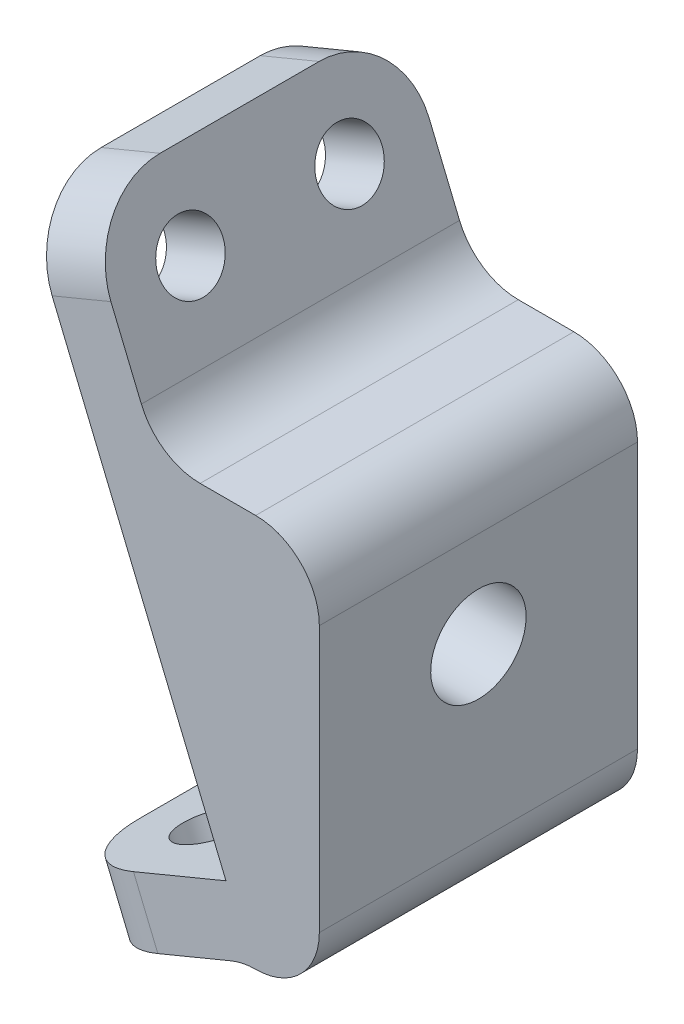
SolidWorks part; units mm, degrees
ref_plane "Front Plane" through (0, 0, 0) normal (0, 0, 1) x (1, 0, 0)
ref_plane "Top Plane" through (0, 0, 0) normal (0, 1, 0) x (1, 0, 0)
ref_plane "Right Plane" through (0, 0, 0) normal (1, 0, 0) x (0, 0, -1)
sketch "Sketch1" plane through (0, 0, 0) normal (0, 0, 1) x (1, 0, 0)
  line L0 (-41.4834, 17.183) -> (17.183, 41.4834) construction
  line L1 (-41.4834, 17.183) -> (-17.183, -41.4834) construction
  line L2 (17.183, 41.4834) -> (41.4834, -17.183) construction
  line L3 (-17.183, -41.4834) -> (41.4834, -17.183) construction
  line L4 (-41.4834, 17.183) -> (41.4834, -17.183) construction
  line L5 (17.183, 41.4834) -> (-17.183, -41.4834) construction
  line L6 (-17.183, -41.4834) -> (50.8, -41.4834) construction
  line L7 (50.8, -41.4834) -> (50.8, 41.4834) construction
  line L8 (50.8, 41.4834) -> (17.183, 41.4834) construction
  line L9 (17.183, 41.4834) -> (41.4834, -17.183) construction
  line L10 (41.4834, -17.183) -> (-17.183, -41.4834) construction
  line L11 (17.183, 41.4834) -> (-50.8, 41.4834) construction
  line L12 (-50.8, 41.4834) -> (-50.8, -41.4834) construction
  line L13 (-50.8, -41.4834) -> (-17.183, -41.4834) construction
  line L14 (0, 0) -> (50.8, 0) construction
  line L15 (50.8, 9.525) -> (50.8, -17.0005)
  line L17 (21.0981, 32.0315) -> (41.4834, -17.183)
  line L18 (41.4834, -17.183) -> (24.9233, -24.0424)
  line L19 (21.0981, 32.0315) -> (26.9647, 34.4615)
  line L20 (26.9647, 34.4615) -> (33.0398, 19.795)
  line L22 (24.9233, -24.0424) -> (27.3534, -29.909)
  line L23 (27.3534, -29.909) -> (42.02, -23.8339)
  line L25 (44.45, 15.875) -> (38.9064, 15.875)
  line L26 (44.45, -23.3505) -> (38.1323, -23.3505) construction
  line L27 (44.45, 9.525) -> (44.45, -17.0005) construction
  line L28 (50.8, 9.525) -> (60.325, 9.525) construction
  line L29 (60.325, 9.525) -> (60.325, 0) construction
  line L30 (60.325, 0) -> (50.8, 0) construction
  arc A0 (50.8, 9.525) -> (44.45, 15.875) centre (44.45, 9.525) ccw
  arc A1 (50.8, -17.0005) -> (44.45, -23.3505) centre (44.45, -17.0005) cw
  arc A2 (38.9064, 15.875) -> (33.0398, 19.795) centre (38.9064, 22.225) cw
  arc A3 (44.45, -23.3505) -> (42.02, -23.8339) centre (44.45, -29.7005) ccw
  point P1 (0, 0)
  point P25 (64.3855, 11.5127)
  point P31 (28.1797, 31.5282)
  dimension "D4" = 6.35
  dimension "D1" = 22.5
  dimension "D2" = 101.6
  dimension "D3" = 63.5
  dimension "D5" = 6.35
  dimension "D6" = 15.875
  dimension "D7" = 9.525
extrude "Boss-Extrude1" add sketch "Sketch1" along normal mid plane 31.75
sketch "Sketch3" plane through (35.1998, 14.5802, 0) normal (0.9239, 0.3827, 0) x (0, 0, -1)
  line L0 (-15.875, 21.5194) -> (15.875, 21.5194) construction
  line L1 (-15.875, 5.6444) -> (-15.875, 21.5194) construction
  line L2 (15.875, 5.6444) -> (15.875, 21.5194) construction
  line L3 (-15.875, 13.5819) -> (-15.875, 21.5194)
  line L4 (-15.875, 21.5194) -> (-7.9375, 21.5194)
  line L5 (7.9375, 21.5194) -> (15.875, 21.5194)
  line L6 (15.875, 21.5194) -> (15.875, 13.5819)
  arc A0 (-7.9375, 21.5194) -> (-15.875, 13.5819) centre (-7.9375, 13.5819) ccw
  arc A1 (7.9375, 21.5194) -> (15.875, 13.5819) centre (7.9375, 13.5819) cw
  circle A2 centre (-7.9375, 13.5819) radius 3.2385
  circle A3 centre (7.9375, 13.5819) radius 3.2385
  point P8 (-15.875, 13.5819)
  dimension "D1" = 6.477
extrude "Cut-Extrude1" cut sketch "Sketch3" against normal through all both and the other way through all
sketch "Sketch4" plane through (14.5802, -35.1998, 0) normal (0.3827, -0.9239, 0) x (-0.9239, -0.3827, 0)
  line L0 (-13.8255, -15.875) -> (-29.7005, -15.875) construction
  line L1 (-13.8255, 15.875) -> (-29.7005, 15.875) construction
  line L2 (-13.8255, -15.875) -> (-13.8255, 15.875) construction
  line L3 (-13.8255, -7.9375) -> (-13.8255, -15.875)
  line L4 (-13.8255, -15.875) -> (-21.763, -15.875)
  line L5 (-13.8255, 7.9375) -> (-13.8255, 15.875)
  line L6 (-13.8255, 15.875) -> (-21.763, 15.875)
  line L8 (-34.925, 11.176) -> (-34.925, 4.699) construction
  line L9 (-31.75, 11.176) -> (-38.1, 11.176) construction
  line L10 (-38.1, 4.699) -> (-31.75, 4.699) construction
  line L11 (-21.763, 11.176) -> (-21.763, 4.699) construction
  arc A0 (-21.763, -15.875) -> (-13.8255, -7.9375) centre (-21.763, -7.9375) ccw
  arc A1 (-21.763, 15.875) -> (-13.8255, 7.9375) centre (-21.763, 7.9375) cw
  circle A2 centre (-21.763, -7.9375) radius 3.2385
  circle A3 centre (-21.763, 7.9375) radius 3.2385
  point P13 (-21.763, -15.875)
extrude "Cut-Extrude2" cut sketch "Sketch4" against normal through all both and the other way through all
sketch "Sketch5" plane through (50.8, 0, 0) normal (1, 0, 0) x (0, 0, -1)
  circle A0 centre (0, 0) radius 4.7625
  dimension "D1" = 9.525
extrude "Cut-Extrude3" cut sketch "Sketch5" against normal through all
sketch "Sketch6" plane through (50.8, 0, 0) normal (1, 0, 0) x (0, 0, -1)
  circle A0 centre (0, 0) radius 7.9375
  dimension "D1" = 15.875
extrude "Cut-Extrude4" [suppressed] cut sketch "Sketch6" against normal through all from offset 7.9375 offset against normal yes
